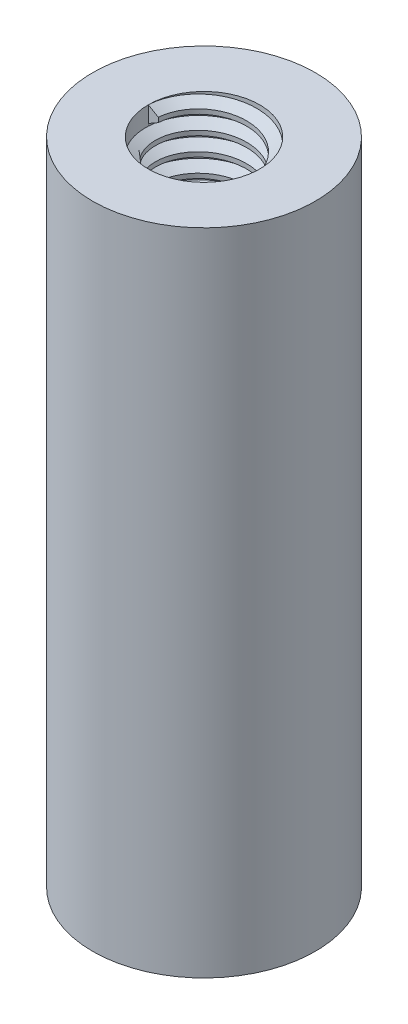
SolidWorks part; units mm, degrees
material "1060 Alloy"
ref_plane "Front Plane" through (0, 0, 0) normal (0, 0, 1) x (1, 0, 0)
ref_plane "Top Plane" through (0, 0, 0) normal (0, 1, 0) x (1, 0, 0)
ref_plane "Right Plane" through (0, 0, 0) normal (1, 0, 0) x (0, 0, -1)
sketch "Sketch1" plane through (0, 0, 0) normal (0, 1, 0) x (1, 0, 0)
  circle A0 centre (0, 0) radius 3
  circle A1 centre (0, 0) radius 6
  dimension "D1" = 12
  dimension "D2" = 6
extrude "Boss-Extrude1" add sketch "Sketch1" along normal blind 35
thread "Thread1" pitch 1 method extrude profile "Thread Profile1" start angle 0, offset 0, length 30, pitch 1, diameter 6
ref_plane "Plane1" through (-3, 35, 0) normal (0, 0, 1) x (-1, 0, 0)
sketch "Thread Profile1" plane through (-3, 35, 0) normal (0, 0, 1) x (-1, 0, 0)
  line L0 (0, 0) -> (0, 1) construction
  line L11 (0, 0) -> (0, 0.875)
  line L12 (0, 0.875) -> (-0.5413, 0.5625)
  line L13 (-0.5413, 0.5625) -> (-0.5413, 0.3125)
  line L15 (-0.5413, 0.3125) -> (0, 0)
  line L17 (-0.5413, 0.4375) -> (0, 0.4375) construction
  point P2 (0, 0)
  dimension "Pitch" = 1
  dimension "Profile_Angle" = 60
  dimension "Profile_Land" = 0.25
  dimension "Profile_Height" = 0.5413
